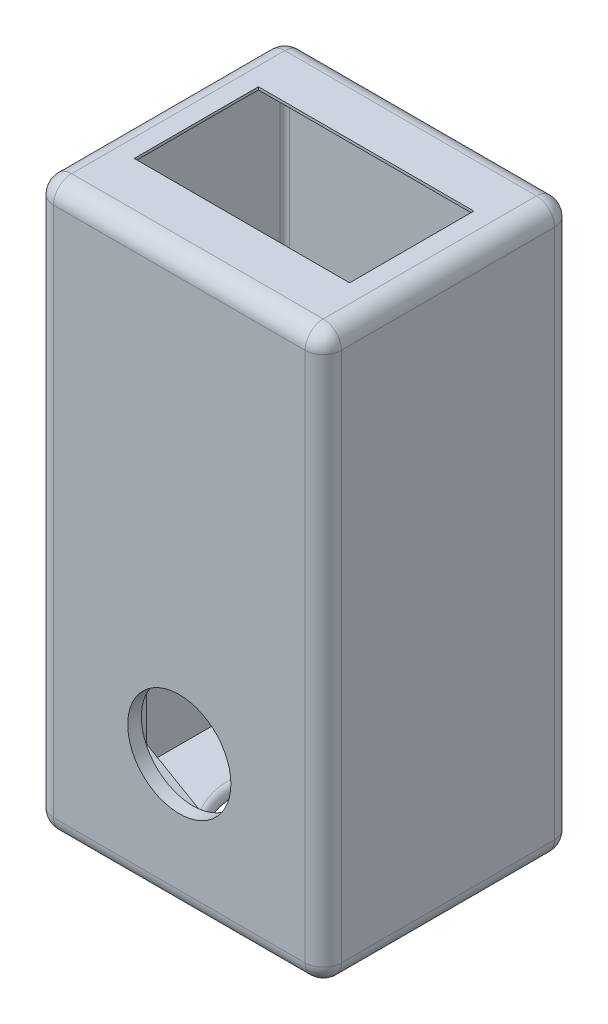
SolidWorks part; units mm, degrees
ref_plane "Front Plane" through (0, 0, 0) normal (0, 0, 1) x (1, 0, 0)
ref_plane "Top Plane" through (0, 0, 0) normal (0, 1, 0) x (1, 0, 0)
ref_plane "Right Plane" through (0, 0, 0) normal (1, 0, 0) x (0, 0, -1)
sketch "Profile Sketch" plane through (0, 0, 0) normal (1, 0, 0) x (0, 0, -1)
  line L0 (0, 0) -> (0, 125)
  line L3 (0, 125) -> (55, 125)
  line L4 (55, 125) -> (55, 0)
  line L5 (55, 0) -> (0, 0)
  dimension "D3" = 55
  dimension "D4" = 125
extrude "Profile Extrude" add sketch "Profile Sketch" along normal mid plane 63.5
sketch "Interior Sketch" plane through (0, 0, 0) normal (0, -1, 0) x (1, 0, 0)
  line L8 (-28.75, -3) -> (-28.75, -52)
  line L9 (-28.75, -52) -> (28.75, -52)
  line L10 (28.75, -52) -> (28.75, -3)
  line L11 (28.75, -3) -> (-28.75, -3)
  line L12 (-28.75, -3) -> (-28.75, -52)
  line L13 (-28.75, -52) -> (28.75, -52)
  line L14 (28.75, -52) -> (28.75, -3)
  line L15 (28.75, -3) -> (-28.75, -3)
  dimension "D1" = 3
extrude "Interior Cut" cut sketch "Interior Sketch" against normal offset from surface (121.4 mm away) 0.6 from offset 3 up to face at (0, 125, -27.5) offset against normal yes
sketch "Opening Sketch" plane through (0, 125, 0) normal (0, 1, 0) x (1, 0, 0)
  line L0 (31.75, 0) -> (-31.75, 55) construction
  line L1 (-23.75, 13.8) -> (23.75, 41.2) construction
  line L12 (-23.75, 13.8) -> (23.75, 13.8)
  line L13 (-23.75, 41.2) -> (-23.75, 13.8)
  line L14 (23.75, 41.2) -> (-23.75, 41.2)
  line L15 (23.75, 13.8) -> (23.75, 41.2)
  point P2 (23.6466, 34.3454)
  point P3 (0, 27.5)
  point P4 (-22.1176, 5.9245)
  dimension "D1" = 27.4
  dimension "D2" = 47.5
extrude "Power Switch Opening Cut" cut sketch "Opening Sketch" against normal up to next
chamfer "Inside Top Chamfer 1" distance 5 angle 45 2 edges at (28.75, 124.4, -27.5) (-28.75, 124.4, -27.5)
chamfer "Inside Top Chamfer 2" distance 10.8 angle 45 2 edges at (0, 124.4, -52) (0, 124.4, -3)
sketch "Stop Button Hole Sketch" plane through (0, 0, 0) normal (0, 0, 1) x (1, 0, 0)
  line L0 (0, 0) -> (0, 30) construction
  circle A0 centre (0, 30) radius 11.375
  dimension "D1" = 22.75
  dimension "D2" = 30
extrude "Stop Button Hole Cut" cut sketch "Stop Button Hole Sketch" against normal up to next
sketch "Stop Button Nut Sketch" plane through (0, 0, 0) normal (0, 0, 1) x (1, 0, 0)
  line L1 (-13.25, 22.3501) -> (0, 14.7002)
  line L2 (0, 14.7002) -> (13.25, 22.3501)
  line L3 (13.25, 22.3501) -> (13.25, 37.6499)
  line L4 (13.25, 37.6499) -> (0, 45.2998)
  line L5 (0, 45.2998) -> (-13.25, 37.6499)
  line L6 (-13.25, 37.6499) -> (-13.25, 22.3501)
  line L7 (0, 8.9267) -> (18.25, 19.4634)
  line L8 (18.25, 19.4634) -> (18.25, 40.5366)
  line L9 (18.25, 40.5366) -> (0, 51.0733)
  line L10 (0, 51.0733) -> (-18.25, 40.5366)
  line L11 (-18.25, 40.5366) -> (-18.25, 19.4634)
  line L12 (-18.25, 19.4634) -> (0, 8.9267)
  circle A0 centre (0, 30) radius 13.25 construction
  circle A1 centre (0, 30) radius 18.25 construction
  point P1 (8.5151, 12.6377)
  dimension "D1" = 26.5
  dimension "D2" = 5
extrude "Nut Recess Extrude" add sketch "Stop Button Nut Sketch" against normal blind 3 from surface starting at face at (0, 18.625, -3)
fillet "Inside Fillets" radius 1 4 edges at (-28.75, 58.3, -3) (28.75, 58.3, -3) (28.75, 58.3, -52) (-28.75, 58.3, -52)
sketch "Wire Outlet Cut Sketch" plane through (0, 0, 0) normal (0, -1, 0) x (1, 0, 0)
  line L0 (-31.75, -55) -> (31.75, 0) construction
  circle A0 centre (0, -27.5) radius 15
  dimension "D1" = 30
extrude "Wire Outlet Cut" cut sketch "Wire Outlet Cut Sketch" against normal up to next
chamfer "Nut Recess Chamfer for Printability" distance 3 angle 45 2 edges at (9.125, 14.195, -3) (-9.125, 14.195, -3)
fillet "Wire Outlet Fillet" 2 edges at (0, 0, -42.5) (0, 3, -42.5) type full round first side face at (0, 0, -42.5) second side face at (0, 3, -42.5) middle face at (0, 0, -42.5)
fillet "Top Fillets" radius 4 12 edges at (0, 0, 0) (31.75, 0, -27.5) (0, 0, -55) (-31.75, 0, -27.5) (-31.75, 62.5, -55) (0, 125, -55) (31.75, 62.5, -55) (-31.75, 62.5, 0) (31.75, 62.5, 0) (-31.75, 125, -27.5) (31.75, 125, -27.5) (0, 125, 0)
